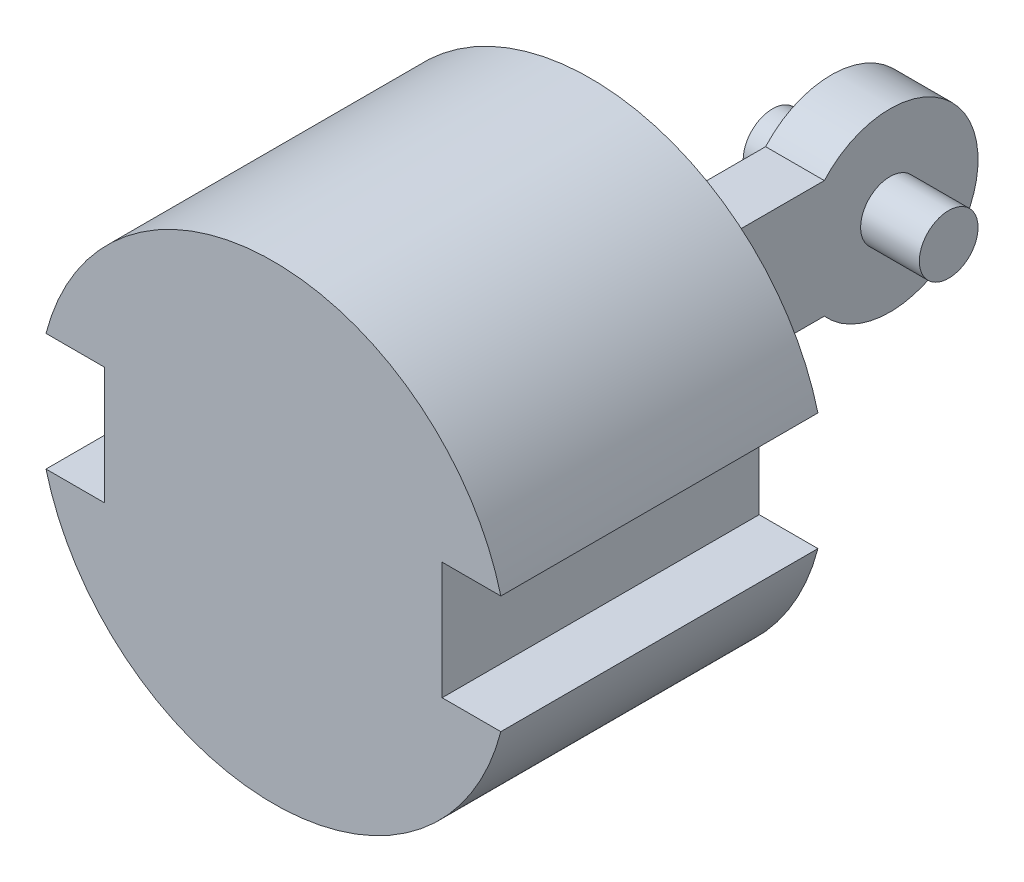
SolidWorks part; units mm, degrees
ref_plane "Front Plane" through (0, 0, 0) normal (0, 0, 1) x (1, 0, 0)
ref_plane "Top Plane" through (0, 0, 0) normal (0, 1, 0) x (1, 0, 0)
ref_plane "Right Plane" through (0, 0, 0) normal (1, 0, 0) x (0, 0, -1)
sketch "Sketch1" plane through (0, 0, 0) normal (0, 0, 1) x (1, 0, 0)
  line L0 (-49.1869, 12.7) -> (-36.4869, 12.7)
  line L1 (-36.4869, 12.7) -> (-36.4869, -12.7)
  line L2 (-36.4869, -12.7) -> (-49.1869, -12.7)
  line L3 (49.1869, 12.7) -> (36.4869, 12.7)
  line L4 (36.4869, 12.7) -> (36.4869, -12.7)
  line L5 (36.4869, -12.7) -> (49.1869, -12.7)
  arc A0 (-49.1869, -12.7) -> (49.1869, -12.7) centre (0, 0) ccw
  arc A1 (49.1869, 12.7) -> (-49.1869, 12.7) centre (0, 0) ccw
  point P9 (-36.4869, 0)
  point P12 (36.4869, 0)
  dimension "D1" = 101.6
  dimension "D2" = 12.7
  dimension "D3" = 25.4
extrude "Boss-Extrude1" add sketch "Sketch1" along normal blind 68.58
sketch "Sketch3" plane through (0, 0, 0) normal (1, 0, 0) x (0, 0, -1)
  line L0 (0, 12.7) -> (44.221, 12.7)
  line L1 (0, -12.7) -> (44.221, -12.7)
  line L2 (0, -12.7) -> (0, 12.7)
  line L3 (-68.58, 12.7) -> (0, 12.7) construction
  line L4 (-68.58, -12.7) -> (0, -12.7) construction
  line L5 (-68.58, -12.7) -> (-68.58, -50.8) construction
  circle A0 centre (58.42, 0) radius 19.05
  circle A1 centre (58.42, 0) radius 6.35
  dimension "D2" = 12.7
  dimension "D3" = 38.1
  dimension "D1" = 127
extrude "Boss-Extrude2" add sketch "Sketch3" along normal mid plane 12.7 contours A0 A1 | A0 L0 L2 L1 region at (0, 0, -20.4717) region at (0, 17.2926, -65.0252)
extrude "Boss-Extrude3" add sketch "Sketch3<3>" along normal mid plane 38.1 contours A1 region at (0, 0, -58.42)
sketch "Sketch3<3>" plane through (0, 0, 0) normal (1, 0, 0) x (0, 0, -1) same geometry as "Sketch3"
equation "\"C\"= 2.7"
